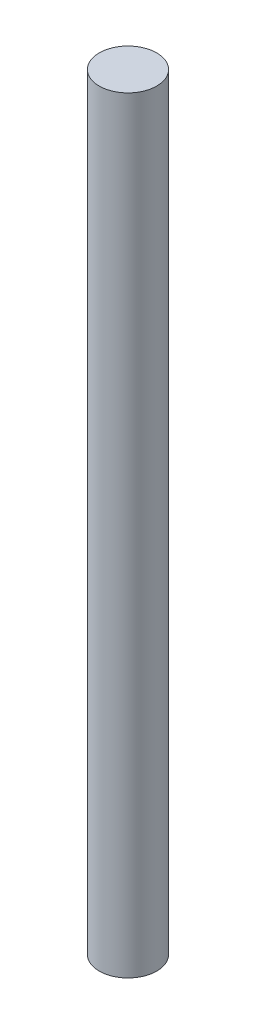
SolidWorks part; units mm, degrees
ref_plane "Front Plane" through (0, 0, 0) normal (0, 0, 1) x (1, 0, 0)
ref_plane "Top Plane" through (0, 0, 0) normal (0, 1, 0) x (1, 0, 0)
ref_plane "Right Plane" through (0, 0, 0) normal (1, 0, 0) x (0, 0, -1)
sketch "Sketch2" plane through (0, 0, 0) normal (0, 1, 0) x (1, 0, 0)
  circle A0 centre (0, 0) radius 0.75
  dimension "D1" = 1.5
extrude "Boss-Extrude1" add sketch "Sketch2" along normal blind 10 and the other way blind 10
